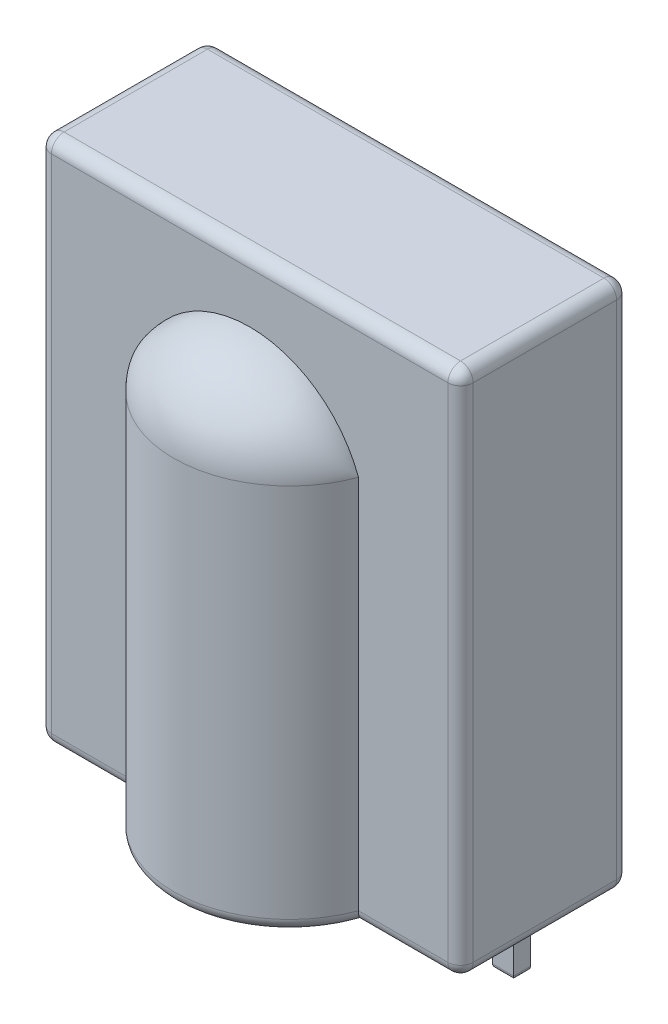
SolidWorks part; units mm, degrees
ref_plane "Спереди" through (0, 0, 0) normal (0, 0, 1) x (1, 0, 0)
ref_plane "Сверху" through (0, 0, 0) normal (0, 1, 0) x (1, 0, 0)
ref_plane "Справа" through (0, 0, 0) normal (1, 0, 0) x (0, 0, -1)
sketch "Эскиз1" plane through (0, 0, 0) normal (0, 1, 0) x (1, 0, 0)
  line L0 (-2.29, 0.2) -> (-2.29, -0.2)
  line L1 (-0.25, 0.2) -> (0.25, 0.2)
  line L2 (-0.25, 0.2) -> (-0.25, -0.2)
  line L3 (-0.25, -0.2) -> (0.25, -0.2)
  line L4 (0.25, 0.2) -> (0.25, -0.2)
  line L5 (-0.25, 0.2) -> (0.25, -0.2) construction
  line L6 (-0.25, -0.2) -> (0.25, 0.2) construction
  line L7 (-2.79, 0.2) -> (-2.79, -0.2)
  line L8 (-2.79, -0.2) -> (-2.29, -0.2)
  line L9 (-2.79, 0.2) -> (-2.29, 0.2)
  line L10 (5.33, 0.2) -> (5.33, -0.2)
  line L11 (4.83, 0.2) -> (4.83, -0.2)
  line L12 (4.83, -0.2) -> (5.33, -0.2)
  line L13 (4.83, 0.2) -> (5.33, 0.2)
  point P0 (0, 0)
  dimension "D1" = 2
  dimension "D2" = 2
extrude "Бобышка-Вытянуть1" add sketch "Эскиз1" along normal blind 0.5
sketch "Эскиз3" plane through (0, 0.5, 0) normal (0, 1, 0) x (1, 0, 0)
  line L1 (-3.73, -2.4) -> (6.27, -2.4)
  line L2 (-3.73, -2.4) -> (-3.73, 1.6)
  line L3 (-3.73, 1.6) -> (6.27, 1.6)
  line L4 (6.27, -2.4) -> (6.27, 1.6)
  line L5 (-3.73, -2.4) -> (6.27, 1.6) construction
  line L6 (-3.73, 1.6) -> (6.27, -2.4) construction
  point P0 (1.27, -0.4)
  point P5 (0, 0)
  point P6 (0, 0)
  point P8 (0, 0)
  point P9 (1.1362, -0.5673)
  point P10 (0, 0)
  point P11 (0, 0)
extrude "Бобышка-Вытянуть2" add sketch "Эскиз3" along normal blind 12.5
sketch "Эскиз4" plane through (0, 0.5, 0) normal (0, -1, 0) x (1, 0, 0)
  line L0 (-3.73, 2.4) -> (6.27, 2.4) construction
  line L1 (6.27, 2.4) -> (3.8507, 2.4)
  line L5 (6.27, -1.6) -> (6.27, 2.4)
  line L6 (6.27, 2.4) -> (-3.73, 2.4)
  line L7 (-3.73, 2.4) -> (-3.73, -1.6)
  line L8 (-3.73, -1.6) -> (6.27, -1.6)
  line L9 (6.27, -1.6) -> (6.27, 2.4)
  line L10 (-1.3107, 2.4) -> (-3.73, 2.4)
  line L11 (-3.73, 2.4) -> (-3.73, -1.6)
  line L12 (-3.73, -1.6) -> (6.27, -1.6)
  arc A0 (-1.3107, 2.4) -> (3.8507, 2.4) centre (1.27, 1.45) cw
  point P5 (0, 0)
  point P6 (0, 0)
  point P7 (0, 0)
  dimension "D1" = 0.95
  dimension "D2" = 2.75
  dimension "D3" = 0
extrude "Бобышка-Вытянуть3" add sketch "Эскиз4" against normal blind 9.2
sketch "Эскиз7" plane through (0, 9.7, 0) normal (0, 1, 0) x (1, 0, 0)
  line L0 (-1.3107, -2.4) -> (3.8507, -2.4)
  arc A0 (-1.3107, -2.4) -> (3.8507, -2.4) centre (1.27, -1.45) ccw
  arc A1 (-1.3107, -2.4) -> (3.8507, -2.4) centre (1.27, -1.45) ccw construction
revolve "Повернуть1" add sketch "Эскиз7" angle 90 about L0 reverse direction yes
fillet "Скругление1" radius 0.3 26 edges at (5.08, 0.5, -0.2) (5.33, 0.5, 0) (5.08, 0.5, 0.2) (4.83, 0.5, 0) (-2.54, 0.5, -0.2) (-2.29, 0.5, 0) (-2.54, 0.5, 0.2) (-2.79, 0.5, 0) (1.27, 0.5, -1.6) (-2.5203, 0.5, 2.4) (1.27, 0.5, 4.2) (5.0603, 0.5, 2.4) (-0.25, 0.5, 0) (0, 0.5, -0.2) (0.25, 0.5, 0) (0, 0.5, 0.2) (-3.73, 6.75, 2.4) (-3.73, 0.5, 0.4) (-3.73, 6.75, -1.6) (6.27, 6.75, -1.6) (6.27, 0.5, 0.4) (6.27, 6.75, 2.4) (1.27, 13, 2.4) (-3.73, 13, 0.4) (1.27, 13, -1.6) (6.27, 13, 0.4)
extrude "Бобышка-Вытянуть4" add sketch "Эскиз1<2>" against normal blind 1 separate body
sketch "Эскиз1<2>" plane through (0, 0, 0) normal (0, 1, 0) x (1, 0, 0) same geometry as "Эскиз1"
fillet "Скругление2" radius 0.1 4 edges at (-2.29, -1, 0) (-2.54, -1, -0.2) (-2.79, -1, 0) (-2.54, -1, 0.2)
fillet "Скругление3" radius 0.1 4 edges at (0, -1, -0.2) (-0.25, -1, 0) (0, -1, 0.2) (0.25, -1, 0)
fillet "Скругление4" radius 0.1 4 edges at (5.33, -1, 0) (5.08, -1, -0.2) (4.83, -1, 0) (5.08, -1, 0.2)
